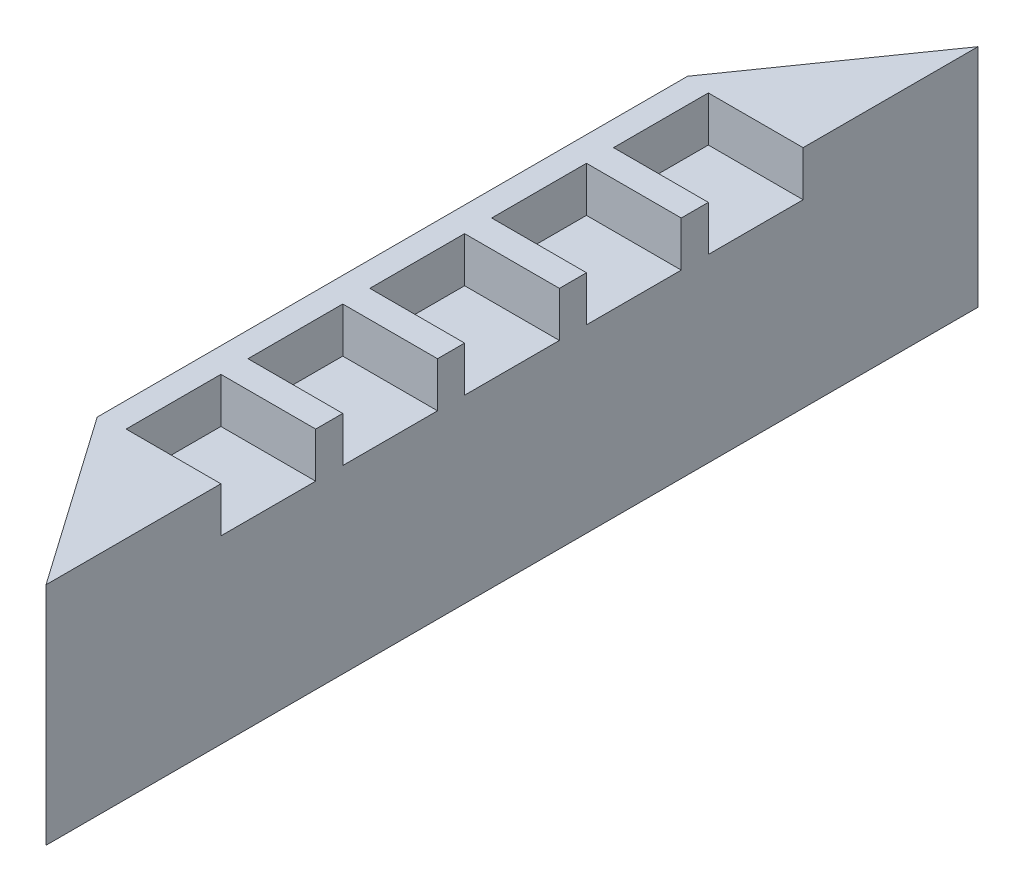
SolidWorks part; units mm, degrees
ref_plane "前视基准面" through (0, 0, 0) normal (0, 0, 1) x (1, 0, 0)
ref_plane "上视基准面" through (0, 0, 0) normal (0, 1, 0) x (1, 0, 0)
ref_plane "右视基准面" through (0, 0, 0) normal (1, 0, 0) x (0, 0, -1)
sketch "草图1" plane through (0, 0, 0) normal (0, 1, 0) x (1, 0, 0)
  line L0 (0, 1032.5) -> (0, -1032.5)
  line L1 (0, -1032.5) -> (-265, -654.0408)
  line L2 (-265, -654.0408) -> (-265, 654.0408)
  line L3 (-265, 654.0408) -> (0, 1032.5)
  line L4 (0, 0) -> (-265, 0) construction
  dimension "D1" = 2065
  dimension "D2" = 265
  dimension "D3" = 145
extrude "凸台-拉伸1" add sketch "草图1" along normal blind 500
sketch "草图2" plane through (0, 0, 0) normal (0, 0, 1) x (1, 0, 0)
  line L0 (-210, 500) -> (-210, 400)
  line L1 (-265, 500) -> (0, 500) construction
  line L2 (-210, 400) -> (0, 400)
  line L3 (0, 500) -> (0, 0) construction
  line L4 (0, 400) -> (0, 500)
  line L5 (0, 500) -> (-210, 500)
  dimension "D1" = 100
  dimension "D2" = 210
extrude "切除-拉伸1" cut sketch "草图2" against normal blind 105 and the other way blind 105
pattern_linear "阵列(线性)1" count 3 spacing 270 along (0, 0, 1) count 3 spacing 270 along (0, 0, -1) of "切除-拉伸1"
